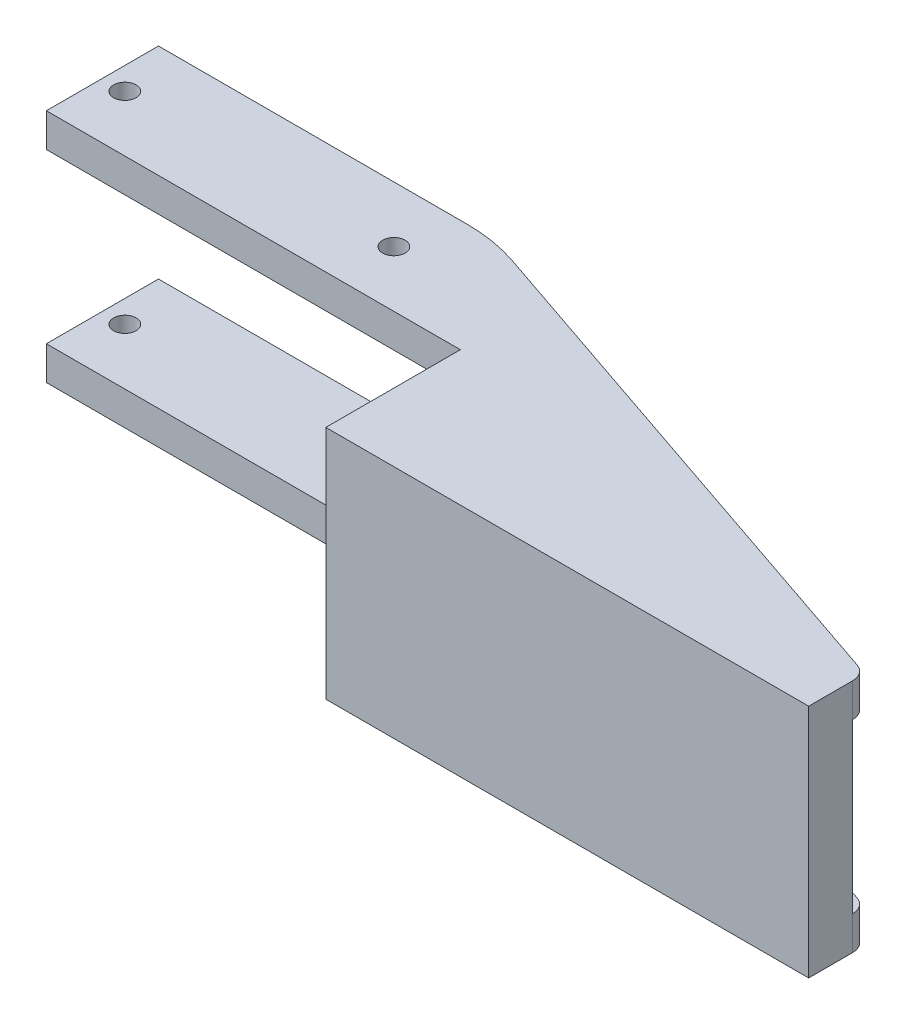
SolidWorks part; units mm, degrees
ref_plane "Front Plane" through (0, 0, 0) normal (0, 0, 1) x (1, 0, 0)
ref_plane "Top Plane" through (0, 0, 0) normal (0, 1, 0) x (1, 0, 0)
ref_plane "Right Plane" through (0, 0, 0) normal (1, 0, 0) x (0, 0, -1)
sketch "Sketch1" plane through (0, 0, 0) normal (0, 1, 0) x (1, 0, 0)
  line L0 (-4.5779, 9.3563) -> (42.0567, -6.4995)
  line L1 (-36.9262, 10.1547) -> (-9.4065, 10.1547)
  line L2 (-36.9262, 10.1547) -> (-36.9262, 0.1547)
  line L3 (0, -11.8453) -> (43.0738, -11.8453)
  line L4 (43.0738, -7.9196) -> (43.0738, -11.8453)
  line L5 (-36.9262, 10.1547) -> (43.0738, -11.8453) construction
  line L6 (-3.5929, 0.1547) -> (26.2671, -1.131) construction
  line L10 (-36.9262, 0.1547) -> (0, 0.1547)
  line L11 (0, -11.8453) -> (0, 0.1547)
  arc A0 (-9.4065, 10.1547) -> (-4.5779, 9.3563) centre (-9.4065, -4.8453) cw
  arc A1 (42.0567, -6.4995) -> (43.0738, -7.9196) centre (41.5738, -7.9196) cw
  point P0 (0, 0)
  point P10 (-6.9262, 10.1547)
  point P13 (43.0738, -6.8453)
  dimension "D6" = 15
  dimension "D7" = 1.5
  dimension "D1" = 10
  dimension "D2" = 80
  dimension "D3" = 5
  dimension "D4" = 50
  dimension "D5" = 10.7143
  dimension "D8" = 12
  dimension "D9" = 33.3333
extrude "Boss-Extrude1" add sketch "Sketch1" against normal blind 3
extrude "Boss-Extrude2" add sketch "Sketch1<2>" along normal blind 3 from offset 15 separate body
sketch "Sketch1<2>" plane through (0, 0, 0) normal (0, 1, 0) x (1, 0, 0) same geometry as "Sketch1"
hole_wizard "Ø2.0mm Clearance Dowel Hole1" positions "Sketch2" profile "Sketch3" hole size "Ø2.0" standard "ANSI Metric" end condition through all
sketch "Sketch2" plane through (0, -3, 0) normal (0, -1, 0) x (-1, 0, 0)
  line L0 (36.9262, 10.1547) -> (36.9262, 0.1547) construction
  point P0 (34.9262, 5.1547)
  point P2 (10.9262, 5.1547)
  point P7 (36.9262, 5.1547)
  dimension "D1" = 2
  dimension "D2" = 24
sketch "Sketch3" plane through (-34.9262, -3, -5.1547) normal (1, 0, 0) x (0, 0, -1)
  line L0 (0, 0) -> (0, 21)
  line L1 (0, 21) -> (1, 21)
  line L2 (1, 21) -> (1, 0)
  line L5 (1, 0) -> (0, 0)
  line L11 (0, -6.35) -> (0, 107.95) construction
  dimension "Thru Hole Dia." = 2
  dimension "Thru Hole Depth" = 21
sketch "Sketch5" plane through (0, 0, 0) normal (0, 1, 0) x (1, 0, 0)
  line L1 (0, -11.8453) -> (43.0738, -11.8453)
  line L2 (0, -11.8453) -> (0, -7.9196)
  line L3 (0, -7.9196) -> (43.0738, -7.9196)
  line L4 (43.0738, -11.8453) -> (43.0738, -7.9196)
extrude "Boss-Extrude3" add sketch "Sketch5" along normal up to surface (15 mm away) up to face at (-34.9262, 15, -6.1547)
